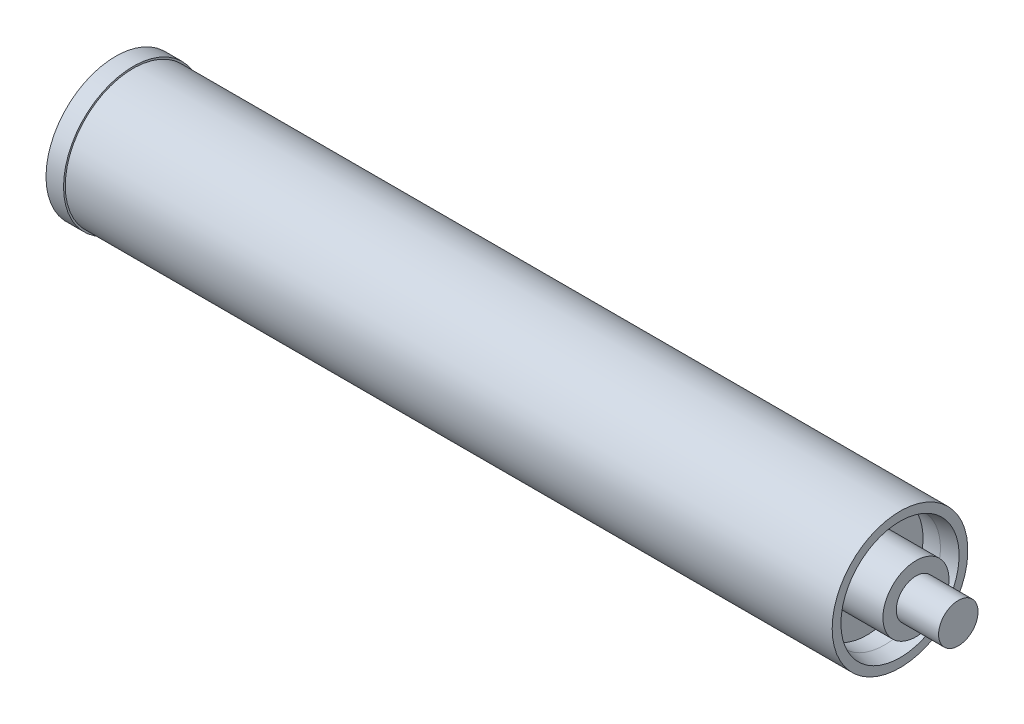
SolidWorks part; units mm, degrees
ref_plane "Plan de face" through (0, 0, 0) normal (0, 0, 1) x (1, 0, 0)
ref_plane "Plan de dessus" through (0, 0, 0) normal (0, 1, 0) x (1, 0, 0)
ref_plane "Plan de droite" through (0, 0, 0) normal (1, 0, 0) x (0, 0, -1)
sketch "Esquisse2" plane through (0, 0, 0) normal (0, 0, 1) x (1, 0, 0)
  line L0 (0, 0) -> (97.8436, 0) construction
  line L1 (0, -26) -> (0, 26) construction
  line L2 (0, 26) -> (12.7, 26)
  line L3 (12.7, 26) -> (12.7, 50.419) construction
  line L4 (12.7, 50.419) -> (25.4, 50.419)
  line L5 (25.4, 50.419) -> (25.4, 49.149)
  line L6 (25.4, 49.149) -> (581.025, 49.149)
  line L7 (581.025, 49.149) -> (581.025, 42.8202)
  line L8 (581.025, 42.8202) -> (569.7021, 40.5731)
  line L9 (569.7021, 40.5731) -> (557.1296, 40.5731)
  line L10 (557.1296, 40.5731) -> (557.1296, 23.9395)
  line L11 (557.1296, 23.9395) -> (592.5977, 23.9395)
  line L12 (592.5977, 23.9395) -> (592.5977, 14.2875)
  line L13 (592.5977, 14.2875) -> (623.2652, 14.2875)
  line L14 (623.2652, 14.2875) -> (623.2652, -14.2875) construction
  line L15 (623.2652, 0) -> (0, 0) construction
  line L16 (592.5977, -14.2875) -> (623.2652, -14.2875) construction
  line L17 (592.5977, -23.9395) -> (592.5977, -14.2875) construction
  line L18 (557.1296, -23.9395) -> (592.5977, -23.9395) construction
  line L19 (557.1296, -40.5731) -> (557.1296, -23.9395) construction
  line L20 (569.7021, -40.5731) -> (557.1296, -40.5731) construction
  line L21 (581.025, -42.8202) -> (569.7021, -40.5731) construction
  line L22 (581.025, -49.149) -> (581.025, -42.8202) construction
  line L23 (25.4, -49.149) -> (581.025, -49.149) construction
  line L24 (25.4, -50.419) -> (25.4, -49.149) construction
  line L25 (12.7, -50.419) -> (25.4, -50.419) construction
  line L26 (12.7, -26) -> (12.7, -50.419) construction
  line L27 (0, -26) -> (12.7, -26) construction
  line L28 (12.7, 50.419) -> (12.7, 38.2095)
  line L29 (12.7, 38.2095) -> (25.4, 35.6891)
  line L30 (25.4, 35.6891) -> (36.5674, 35.6891)
  line L31 (36.5674, 35.6891) -> (36.5674, 26)
  line L32 (36.5674, 26) -> (12.7, 26)
  line L33 (25.4, 35.6891) -> (25.4, 49.149) construction
  line L34 (36.5674, -26) -> (12.7, -26) construction
  line L35 (36.5674, -35.6891) -> (36.5674, -26) construction
  line L36 (25.4, -35.6891) -> (36.5674, -35.6891) construction
  line L37 (12.7, -38.2095) -> (25.4, -35.6891) construction
  line L38 (12.7, -50.419) -> (12.7, -38.2095) construction
  line L39 (0, 26) -> (0, 0)
  line L40 (0, 0) -> (623.2652, 0)
  line L41 (623.2652, 0) -> (623.2652, 14.2875)
  point P2 (-0.1063, 35.6891)
  dimension "D2" = 30.6675
  dimension "D3" = 42.2402
  dimension "D4" = 28.575
  dimension "D5" = 47.879
  dimension "D6" = 98.298
  dimension "D7" = 12.7
  dimension "D8" = 100.838
  dimension "D9" = 12.7
  dimension "D10" = 52
  dimension "D11" = 66.1356
  dimension "D12" = 12.5725
  dimension "D13" = 16.6336
  dimension "D14" = 11.5437
  dimension "D15" = 36.5674
  dimension "D16" = 597.8652
revolve "Révolution7" add sketch "Esquisse2" angle 360 about L0
sketch "Esquisse3" plane through (0, 0, 0) normal (0, 0, 1) x (1, 0, 0)
  line L0 (0, 0) -> (623.2652, 0) construction
  line L1 (623.2652, -14.2875) -> (623.2652, 14.2875) construction
  line L2 (0, 20) -> (0, 0)
  line L3 (0, 26) -> (0, -26) construction
  line L4 (0, 0) -> (557.1296, 0)
  line L5 (557.1296, 0) -> (557.1296, 12.9578)
  line L6 (557.1296, -40.5731) -> (557.1296, 40.5731) construction
  line L7 (557.1296, 12.9578) -> (539.7791, 12.9578)
  line L8 (539.7791, 12.9578) -> (539.7791, 44.271)
  line L9 (539.7791, 44.271) -> (65.8719, 44.271)
  line L10 (65.8719, 44.271) -> (34.083, 14.3276)
  line L11 (34.083, 14.3276) -> (19.083, 14.3276)
  line L12 (19.083, 14.3276) -> (0, 20)
  line L13 (36.5674, 26) -> (0, 26) construction
  dimension "D1" = 15
  dimension "D2" = 6
  dimension "D3" = 17.3505
  dimension "D4" = 19.083
  dimension "D5" = 19.9082
  dimension "D6" = 43.6708
  dimension "D7" = 29.9434
  dimension "D8" = 12.9578
revolve "Enlèvement de matière-Révolution1" cut sketch "Esquisse3" angle 360 about L0
